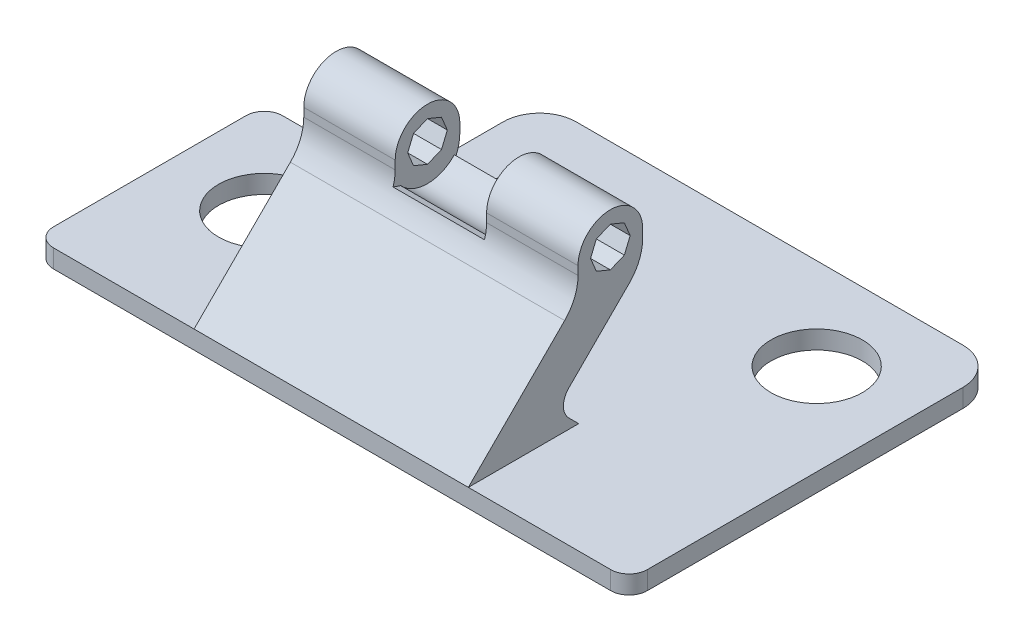
SolidWorks part; units mm, degrees
ref_plane "Front Plane" through (0, 0, 0) normal (0, 0, 1) x (1, 0, 0)
ref_plane "Top Plane" through (0, 0, 0) normal (0, 1, 0) x (1, 0, 0)
ref_plane "Right Plane" through (0, 0, 0) normal (1, 0, 0) x (0, 0, -1)
sketch "Sketch1" plane through (0, 0, 0) normal (0, 1, 0) x (1, 0, 0)
  line L0 (-30.372, 4.8519) -> (-20.222, 4.8519)
  line L5 (-30.372, -20.1981) -> (30.578, -20.1981)
  line L6 (-32.372, -18.1981) -> (-32.372, 2.8519)
  line L7 (-17.722, 20.3266) -> (32.578, 20.3266)
  line L16 (32.578, -18.1981) -> (32.578, 20.3266)
  line L17 (-32.372, -20.1981) -> (32.578, 20.3266) construction
  line L18 (-17.722, 10.9875) -> (32.578, -20.1981) construction
  line L19 (-17.722, 7.3519) -> (-17.722, 20.3266)
  arc A0 (30.578, -20.1981) -> (32.578, -18.1981) centre (30.578, -18.1981) ccw
  arc A1 (-30.372, -20.1981) -> (-32.372, -18.1981) centre (-30.372, -18.1981) cw
  arc A2 (-30.372, 4.8519) -> (-32.372, 2.8519) centre (-30.372, 2.8519) ccw
  arc A3 (-20.222, 4.8519) -> (-17.722, 7.3519) centre (-20.222, 7.3519) ccw
  point P0 (0, 0)
  dimension "D1" = 25.05
  dimension "D5" = 14.65
  dimension "D3" = 2
  dimension "D4" = 2.5
  dimension "D2" = 64.95
  dimension "D6" = 50.3
extrude "Boss-Extrude2" add sketch "Sketch1" along normal blind 2
sketch "Sketch2" plane through (0, 0, 0) normal (1, 0, 0) x (0, 0, -1)
  line L0 (-20.1981, 2) -> (-8.1981, 14) construction
  line L1 (-18.1981, 2) -> (20.3266, 2) construction
  line L2 (-20.1981, 2) -> (-8.1981, 14)
  line L4 (-1.1271, 14) -> (-13.1271, 2)
  line L5 (-13.1271, 2) -> (-20.1981, 2)
  line L9 (-8.1981, 14) -> (-8.1981, 17)
  line L11 (-1.1271, 14) -> (-1.1271, 17)
  line L12 (-4.6626, 14.8352) -> (-3.1319, 15.4693)
  line L13 (-3.1319, 15.4693) -> (-2.4978, 17)
  line L14 (-2.4978, 17) -> (-3.1319, 18.5307)
  line L15 (-3.1319, 18.5307) -> (-4.6626, 19.1648)
  line L16 (-4.6626, 19.1648) -> (-6.1933, 18.5307)
  line L17 (-6.1933, 18.5307) -> (-6.8274, 17)
  line L18 (-6.8274, 17) -> (-6.1933, 15.4693)
  line L19 (-6.1933, 15.4693) -> (-4.6626, 14.8352)
  arc A0 (-8.1981, 17) -> (-1.1271, 17) centre (-4.6626, 17) cw
  circle A2 centre (-4.6626, 17) radius 2 construction
  dimension "D3" = 3.5355
  dimension "D7" = 4
  dimension "D1" = 45
  dimension "D2" = 45
  dimension "D5" = 3
  dimension "D6" = 7.0711
extrude "Boss-Extrude3" add sketch "Sketch2" along normal mid plane 30
chamfer "Chamfer1" distance 5 angle 45 1 edges at (0, 2, 13.1271)
fillet "Fillet2" radius 5 2 edges at (0, 14, 8.1981) (0, 14, 1.1271)
fillet "Fillet3" radius 2 1 edges at (0, 4.5, 10.6271)
sketch "Sketch4" plane through (0, 0, 0) normal (1, 0, 0) x (0, 0, -1)
  line L0 (-6.8274, 17) -> (-2.4978, 17) construction
  circle A1 centre (-4.6626, 17) radius 4
sketch "Sketch6" plane through (0, 2, 0) normal (0, 1, 0) x (1, 0, 0)
  line L0 (32.578, -18.1981) -> (32.578, 20.3266) construction
  line L1 (32.578, 20.3266) -> (-17.722, 20.3266) construction
  line L2 (-17.722, 20.3266) -> (-17.722, 7.3519) construction
  line L3 (-20.222, 4.8519) -> (-30.372, 4.8519) construction
  line L4 (-32.372, 2.8519) -> (-32.372, -18.1981) construction
  circle A0 centre (22.578, 10.3266) radius 5
  circle A1 centre (-7.722, 10.3266) radius 5
  circle A2 centre (-22.372, -5.1481) radius 5
  dimension "D1" = 10
  dimension "D2" = 10
  dimension "D3" = 10
  dimension "D4" = 10
  dimension "D5" = 10
  dimension "D6" = 10
extrude "Cut-Extrude5" cut sketch "Sketch6" against normal through all
fillet "Fillet4" radius 4 2 edges at (32.578, 1, -20.3266) (-17.722, 1, -20.3266)
extrude "Cut-Extrude6" cut sketch "Sketch4" against normal mid plane 10
chamfer "Chamfer2" distance 1 angle 45 1 edges at (0, 14.879, 1.2713)
chamfer "Chamfer3" distance 1 angle 45 1 edges at (0, 15.2601, 8.2644)
